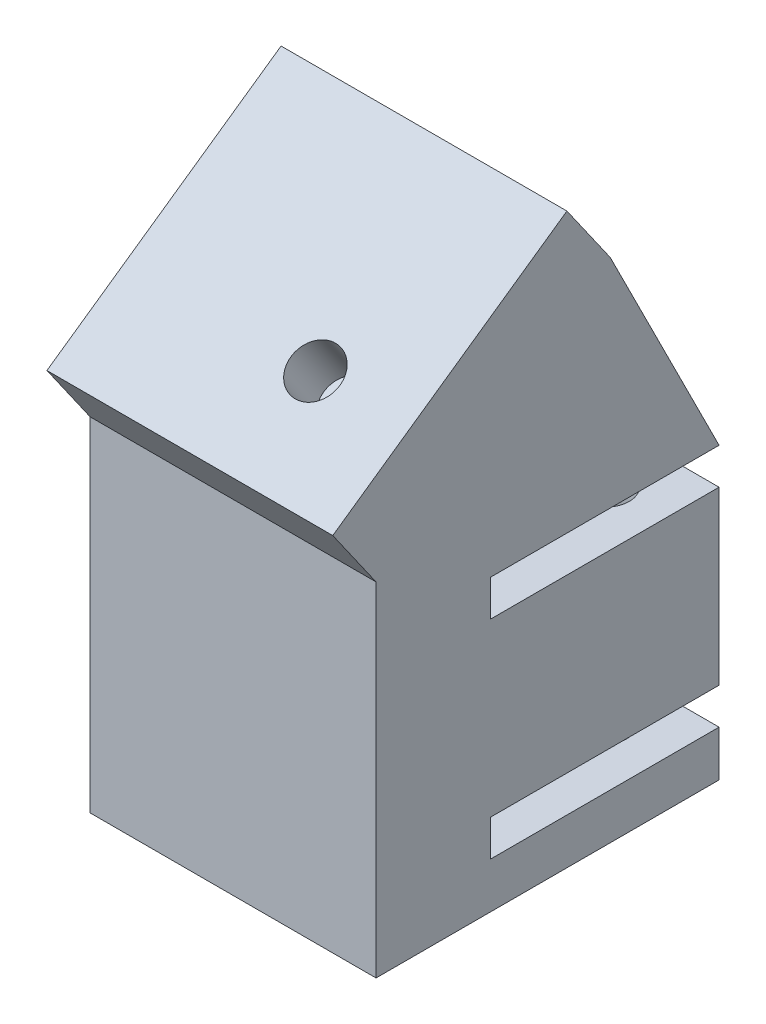
SolidWorks part; units mm, degrees
ref_plane "Front Plane" through (0, 0, 0) normal (0, 0, 1) x (1, 0, 0)
ref_plane "Top Plane" through (0, 0, 0) normal (0, 1, 0) x (1, 0, 0)
ref_plane "Right Plane" through (0, 0, 0) normal (1, 0, 0) x (0, 0, -1)
sketch "Sketch1" plane through (0, 0, 0) normal (1, 0, 0) x (0, 0, -1)
  line L0 (20, 0) -> (0, 0)
  line L1 (20, 0) -> (20, -15)
  line L2 (20, -15) -> (0, -15)
  line L3 (0, -15) -> (0, -18.175)
  line L4 (0, -18.175) -> (20, -18.175)
  line L5 (20, -18.175) -> (20, -22.175)
  line L6 (20, -22.175) -> (-10, -22.175)
  line L7 (-10, -22.175) -> (-10, 7.825)
  line L8 (-10, 7.825) -> (10.4788, 22.1644)
  line L10 (0, 0) -> (0, 3.175)
  line L11 (0, 3.175) -> (20, 3.175)
  line L12 (20, 3.175) -> (10.4788, 22.1644)
  point P0 (10.4788, 20.7224)
  dimension "D1" = 3.175
  dimension "D2" = 15
  dimension "D3" = 4
  dimension "D4" = 20
  dimension "D5" = 30
  dimension "D6" = 25
  dimension "D7" = 125
  dimension "D8" = 30
extrude "Boss-Extrude1" add sketch "Sketch1" along normal blind 25
sketch "Sketch2" plane through (0, 9.9491, 6.9664) normal (0, 0.8192, 0.5736) x (1, 0, 0)
  line L1 (0, 21.2967) -> (21, 21.2967)
  line L2 (0, 21.2967) -> (0, 0.2967)
  line L3 (0, 0.2967) -> (21, 0.2967)
  line L4 (21, 21.2967) -> (21, 0.2967)
  line L5 (0, 21.2967) -> (25, 21.2967)
  line L6 (0, 21.2967) -> (0, -3.7033)
  line L7 (0, -3.7033) -> (25, -3.7033)
  line L8 (25, 21.2967) -> (25, -3.7033)
  line M5 (0, 21.2967) -> (0, -3.7033)
  line M6 (0, -3.7033) -> (25, -3.7033)
  line M7 (25, -3.7033) -> (25, 21.2967)
  line M8 (25, 21.2967) -> (0, 21.2967)
  dimension "D1" = 4
  dimension "D2" = 4
extrude "Boss-Extrude2" add sketch "Sketch2" along normal blind 1.6 contours L4 L3 M8 M5 M6 M7 region at (23, 21.9616, -10.1892)
sketch "Sketch3" plane through (0, 11.2598, 7.8842) normal (0, 0.8192, 0.5736) x (1, 0, 0)
  line L1 (25, -3.7033) -> (0, -3.7033)
  line L2 (25, -3.7033) -> (25, 21.2967)
  line L3 (25, 21.2967) -> (0, 21.2967)
  line L4 (0, -3.7033) -> (0, 21.2967)
extrude "Boss-Extrude3" add sketch "Sketch3" along normal blind 5
sketch "Sketch4" plane through (0, 15.3555, 10.7521) normal (0, 0.8192, 0.5736) x (1, 0, 0)
  line L0 (25, -3.7033) -> (25, 21.2967) construction
  line L1 (0, -3.7033) -> (25, -3.7033) construction
  circle A0 centre (16.6, 4.6967) radius 2.15
  dimension "D1" = 4.3
  dimension "D2" = 8.4
  dimension "D3" = 8.4
extrude "Cut-Extrude1" cut sketch "Sketch4" against normal up to surface (5 mm away) up to face at (10.5, 17.4525, -0.96)
sketch "Sketch5" plane through (0, 15.3555, 10.7521) normal (0, 0.8192, 0.5736) x (1, 0, 0)
  circle A0 centre (16.6, 4.6967) radius 1.85
  dimension "D1" = 3.7
extrude "Cut-Extrude2" cut sketch "Sketch5" against normal blind 13
sketch "Sketch6" plane through (0, -18.175, 0) normal (0, 1, 0) x (1, 0, 0)
  line L0 (0, 20) -> (0, 10.4788) construction
  line L1 (25, 20) -> (0, 20) construction
  line L2 (25, 20) -> (25, 10.4788) construction
  circle A0 centre (5, 15) radius 1.85
  circle A1 centre (20, 15) radius 1.85
  dimension "D1" = 3.7
  dimension "D2" = 3.7
  dimension "D3" = 5
  dimension "D4" = 5
  dimension "D5" = 5
  dimension "D6" = 5
extrude "Cut-Extrude3" cut sketch "Sketch6" against normal blind 13
sketch "Sketch7" plane through (0, -15, 0) normal (0, -1, 0) x (1, 0, 0)
  circle A0 centre (5, -15) radius 2.15
  circle A1 centre (20, -15) radius 2.15
  dimension "D1" = 4.3
extrude "Cut-Extrude4" cut sketch "Sketch7" against normal blind 43
sketch "Sketch8" plane through (0, 0, 0) normal (0, 1, 0) x (1, 0, 0)
  circle A0 centre (5, 15) radius 4
  circle A1 centre (20, 15) radius 4
  dimension "D1" = 8
extrude "Cut-Extrude5" cut sketch "Sketch8" along normal blind 67 from offset 7
equation "\"D2@Sketch6\"=\"D1@Sketch6\""
